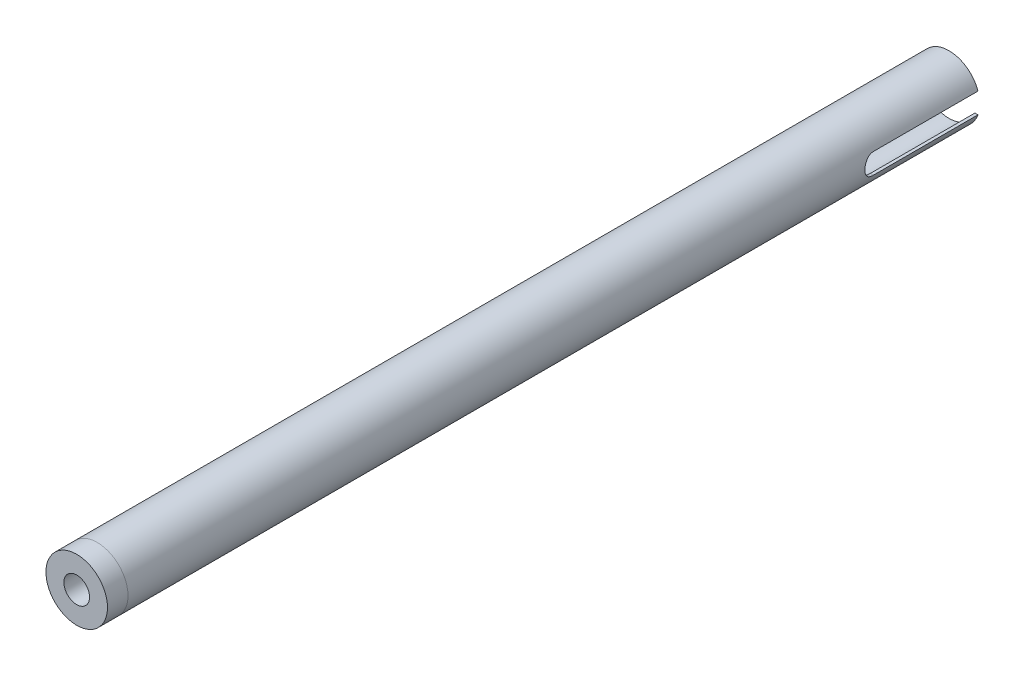
SolidWorks part; units mm, degrees
material "AISI 4130 Steel, annealed at 865C"
ref_plane "Front Plane" through (0, 0, 0) normal (0, 0, 1) x (1, 0, 0)
ref_plane "Top Plane" through (0, 0, 0) normal (0, 1, 0) x (1, 0, 0)
ref_plane "Right Plane" through (0, 0, 0) normal (1, 0, 0) x (0, 0, -1)
sketch "Axis" plane through (0, 0, 0) normal (0, 1, 0) x (1, 0, 0)
  line L0 (0, 0) -> (0, 270.0365) construction
  line L1 (0, 0) -> (0, -28.575) construction
  line L2 (0, 270.0365) -> (-9.525, 270.0365) construction
  line L4 (0, 295.0656) -> (-10.414, 267.7005) construction
  dimension "D1" = 28.575
  dimension "D2" = 9.525
sketch "Sketch1" plane through (0, 0, 0) normal (0, 0, 1) x (1, 0, 0)
  line L0 (-9.525, 0) -> (9.525, 0) construction
  line L1 (-8.9803, 3.175) -> (8.9803, 3.175)
  line L2 (-8.9803, -3.175) -> (8.9803, -3.175)
  circle A0 centre (0, 0) radius 9.525
  circle A1 centre (0, 0) radius 8.636
  circle A2 centre (0, 0) radius 3.9688
  dimension "D1" = 19.05
  dimension "D3" = 7.9375
  dimension "D2" = 0.889
  dimension "D4" = 6.35
extrude "Threaded insert 1-1" add sketch "Sketch1" against normal blind 6.35 contours A2 L1 A1 | A1 L1 A0 | A2 L0 A1 L1 | A1 L0 A0 L1 | L0 A1 L2 A0 | L0 A2 L2 A1 | A2 L2 A1 | A1 L2 A0 | L0 A1 L2 A2 | L0 A0 L2 A1 | A0 L0 A1 L1 | A1 L0 A2 L1 region at (5.9465, 1.6355, 0) region at (5.9465, -1.6355, 0) region at (8.8881, 1.6046, 0) region at (8.8881, -1.6046, 0) region at (-5.9465, -1.6355, 0) region at (-5.9465, 1.6355, 0) region at (0, 5.5139, 0) region at (0, -5.5139, 0) region at (0, 8.8265, 0) region at (8.5057, -3.3655, 0) region at (-8.8881, -1.6046, 0) region at (-8.8881, 1.6046, 0)
extrude "Threaded insert 1-2" add sketch "Sketch1<3>" against normal blind 9.525 from surface contours A2 L1 A1 | A2 L0 A1 L1 | L0 A2 L2 A1 | A2 L2 A1 | L0 A1 L2 A2 | A1 L0 A2 L1 region at (5.9465, 1.6355, 0) region at (5.9465, -1.6355, 0) region at (-5.9465, -1.6355, 0) region at (-5.9465, 1.6355, 0) region at (0, 5.5139, 0) region at (0, -5.5139, 0) starting at face at (9.525, 0, -6.35)
sketch "Sketch1<3>" plane through (0, 0, 0) normal (0, 0, 1) x (1, 0, 0) same geometry as "Sketch1"
extrude "A-arm tube" add sketch "Sketch1<4>" against normal up to vertex (270.0365 mm away) from surface separate body contours A1 L1 A0 | A1 L0 A0 L1 | L0 A1 L2 A0 | A1 L2 A0 | L0 A0 L2 A1 | A0 L0 A1 L1 region at (8.8881, 1.6046, 0) region at (8.8881, -1.6046, 0) region at (0, 8.8265, 0) region at (8.5057, -3.3655, 0) region at (-8.8881, -1.6046, 0) region at (-8.8881, 1.6046, 0) up to point (0, 0, -270.0365) starting at face at (8.636, 0, -6.35)
sketch "Sketch1<4>" plane through (0, 0, 0) normal (0, 0, 1) x (1, 0, 0) same geometry as "Sketch1"
extrude "Apex slot" cut sketch "Sketch1<5>" along normal blind 35.56 from surface contours A0 L0 A1 L1 | L0 A0 L2 A1 | A1 L0 A0 L1 | L0 A1 L2 A0 region at (8.8881, 1.6046, 0) region at (8.8881, -1.6046, 0) region at (-8.8881, -1.6046, 0) region at (-8.8881, 1.6046, 0) starting at face at (8.636, 0, -270.0365)
sketch "Sketch1<5>" plane through (0, 0, 0) normal (0, 0, 1) x (1, 0, 0) same geometry as "Sketch1"
fillet "Fillet1" radius 3.175 4 edges at (-8.5057, 3.175, -234.4765) (-8.5057, -3.175, -234.4765) (8.5057, -3.175, -234.4765) (8.5057, 3.175, -234.4765)
equation "\"tube diameter\" = 3 / 4"
equation "\"tube thickness\" = .035"
equation "\"apex thickness\"= .25"
equation "\"tube slot\"= 1.4"
equation "\"D1@Sketch1\"=\"tube diameter\""
equation "\"D2@Sketch1\"=\"tube thickness\""
equation "\"threaded insert hole\"= .3125"
equation "\"D3@Sketch1\"=\"threaded insert hole\""
equation "\"D4@Sketch1\"=\"apex thickness\""
equation "\"D1@Apex slot\" = \"tube slot\""
equation "\"D1@Fillet1\"=\"apex thickness\"/2"
equation "\"D2@Axis\"=\"tube diameter\"/2"
